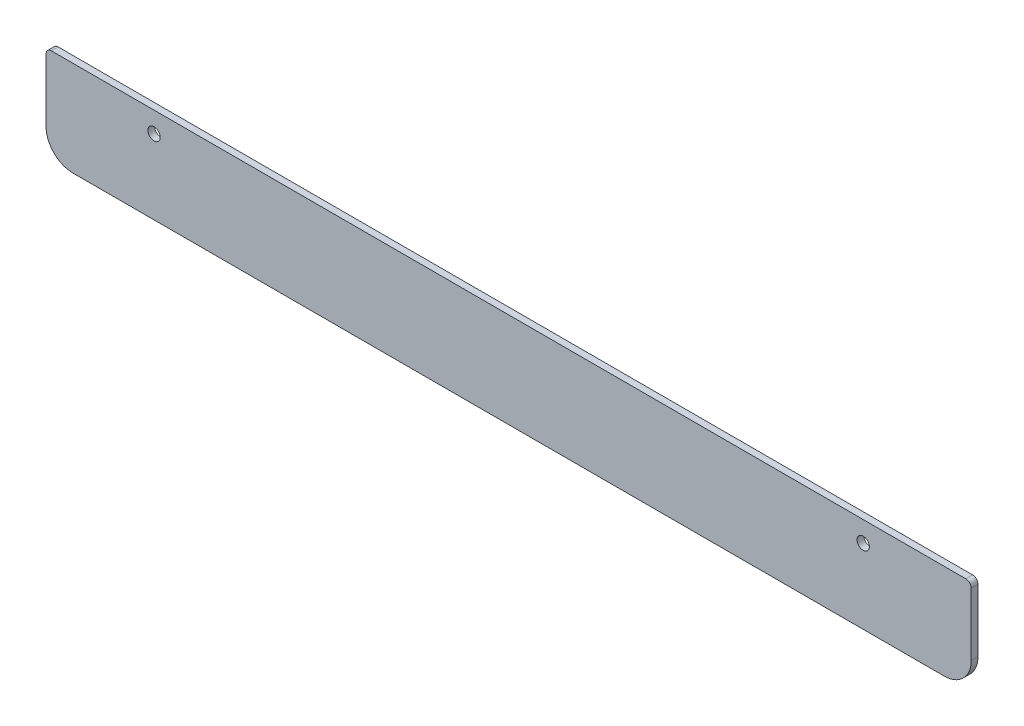
SolidWorks part; units mm, degrees
ref_plane "Front Plane" through (0, 0, 0) normal (0, 0, 1) x (1, 0, 0)
ref_plane "Top Plane" through (0, 0, 0) normal (0, 1, 0) x (1, 0, 0)
ref_plane "Right Plane" through (0, 0, 0) normal (1, 0, 0) x (0, 0, -1)
sketch "Sketch1" plane through (0, 0, 0) normal (0, 0, 1) x (1, 0, 0)
  line L1 (-217.4875, -22.352) -> (217.4875, -22.352)
  line L2 (-217.4875, -22.352) -> (-217.4875, 22.352)
  line L3 (-217.4875, 22.352) -> (217.4875, 22.352)
  line L4 (217.4875, -22.352) -> (217.4875, 22.352)
  line L5 (-217.4875, -22.352) -> (217.4875, 22.352) construction
  line L6 (-217.4875, 22.352) -> (217.4875, -22.352) construction
  point P0 (0, 0)
  dimension "D1" = 44.704
  dimension "D2" = 434.975
extrude "Boss-Extrude1" add sketch "Sketch1" along normal blind 3.175
fillet "Fillet1" radius 12.7 2 edges at (217.4875, -22.352, 1.5875) (-217.4875, -22.352, 1.5875)
hole_wizard "#1 (0.228) Diameter Hole1" positions "Sketch2" profile "Sketch3" hole size "#1" standard "ANSI Inch" end condition through all
sketch "Sketch2" plane through (0, 0, 3.175) normal (0, 0, 1) x (1, 0, 0)
  line L0 (-217.4875, 12.7) -> (217.4875, 12.7) construction
  line L1 (-217.4875, 22.352) -> (-217.4875, -9.652) construction
  line L2 (217.4875, -9.652) -> (217.4875, 22.352) construction
  line L3 (217.4875, 22.352) -> (-217.4875, 22.352) construction
  point P10 (-166.6875, 12.7)
  point P12 (166.6875, 12.7)
  dimension "D1" = 9.652
  dimension "D2" = 333.375
  dimension "D3" = 50.8
sketch "Sketch3" plane through (166.6875, 12.7, 3.175) normal (1, 0, 0) x (0, -1, 0)
  line L0 (0, 0) -> (0, 3.175)
  line L1 (0, 3.175) -> (2.8956, 3.175)
  line L2 (2.8956, 3.175) -> (2.8956, 0)
  line L5 (2.8956, 0) -> (0, 0)
  line L11 (0, -6.35) -> (0, 107.95) construction
  dimension "Thru Hole Dia." = 5.7912
  dimension "Thru Hole Depth" = 3.175
fillet "Fillet2" radius 2.54 2 edges at (217.4875, 22.352, 1.5875) (-217.4875, 22.352, 1.5875)
